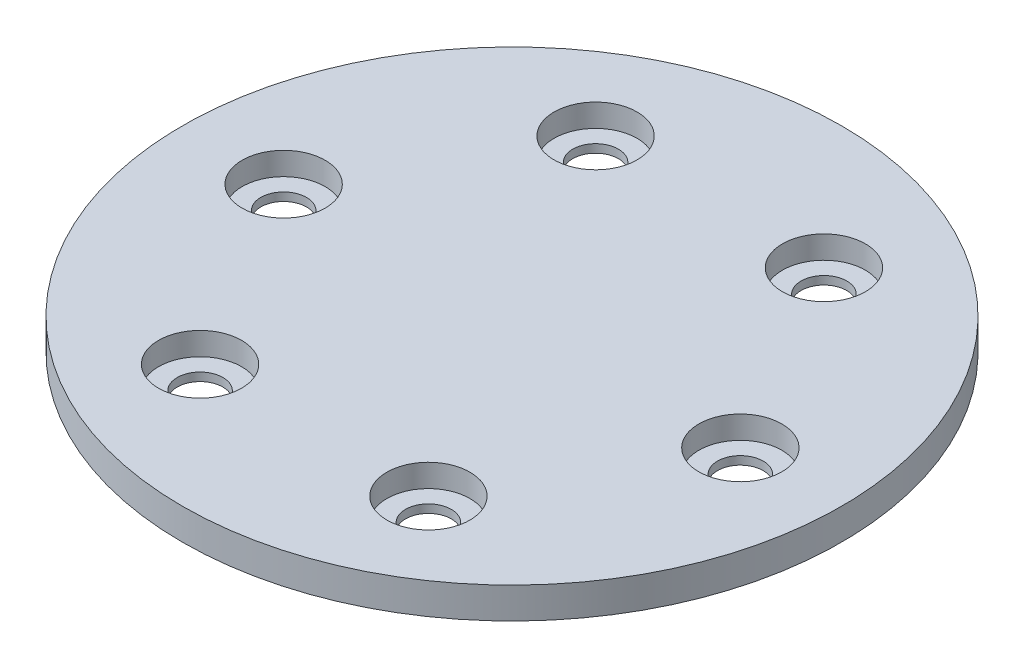
SolidWorks part; units mm, degrees
material "1060 Alloy"
ref_plane "Front Plane" through (0, 0, 0) normal (0, 0, 1) x (1, 0, 0)
ref_plane "Top Plane" through (0, 0, 0) normal (0, 1, 0) x (1, 0, 0)
ref_plane "Right Plane" through (0, 0, 0) normal (1, 0, 0) x (0, 0, -1)
sketch "Sketch1" plane through (0, 0, 0) normal (0, 1, 0) x (1, 0, 0)
  circle A0 centre (0, 0) radius 15.875
  dimension "D1" = 31.75
extrude "Boss-Extrude1" add sketch "Sketch1" along normal blind 1.5
sketch "Sketch7" plane through (0, 1.5, 0) normal (0, 1, 0) x (1, 0, 0)
  circle A0 centre (0, -10.25) radius 0.25
  circle A1 centre (0, 0) radius 9.8
  dimension "D1" = 0.5
  dimension "D2" = 10.25
  dimension "D3" = 19.6
sketch "Sketch8" plane through (0, 1.5, 0) normal (0, 1, 0) x (1, 0, 0)
  line L0 (0, 0) -> (13.2071, 13.2071) construction
  circle A0 centre (7.7782, 7.7782) radius 1
  dimension "D1" = 2
  dimension "D2" = 11
sketch "Sketch9" plane through (0, 1.5, 0) normal (0, 1, 0) x (1, 0, 0)
  circle A0 centre (0, 0) radius 11
  dimension "D1" = 22
hole_wizard "CBORE for M5 Hex Head Bolt1" positions "Sketch13" profile "Sketch14" counterbore size "M5" standard "ISO"
sketch "Sketch13" plane through (0, 1.5, 0) normal (0, 1, 0) x (1, 0, 0)
  circle A0 centre (0, 0) radius 11 construction
  point P0 (-11, 0)
  dimension "D1" = 11
sketch "Sketch14" plane through (-11, 1.5, 0) normal (1, 0, 0) x (0, 0, 1)
  line L0 (0, 0) -> (0, 5.6609)
  line L1 (0, 5.6609) -> (1.1, 5)
  line L2 (1.1, 5) -> (1.1, 1.1)
  line L3 (1.1, 1.1) -> (2, 1.1)
  line L4 (2, 1.1) -> (2, 0)
  line L5 (2, 0) -> (0, 0)
  line L10 (0, 5.6609) -> (-1.1, 5) construction
  line L11 (0, -6.35) -> (0, 107.95) construction
  dimension "Hole Dia." = 2.2
  dimension "Hole Depth" = 5
  dimension "C'Bore Dia." = 4
  dimension "C'Bore Depth" = 1.1
  dimension "Drill Angle" = 118
pattern_circular "CirPattern1" count 6 over 360 about axis through (0, 1.5, 0) along (0, 1, 0) of "CBORE for M5 Hex Head Bolt1"
